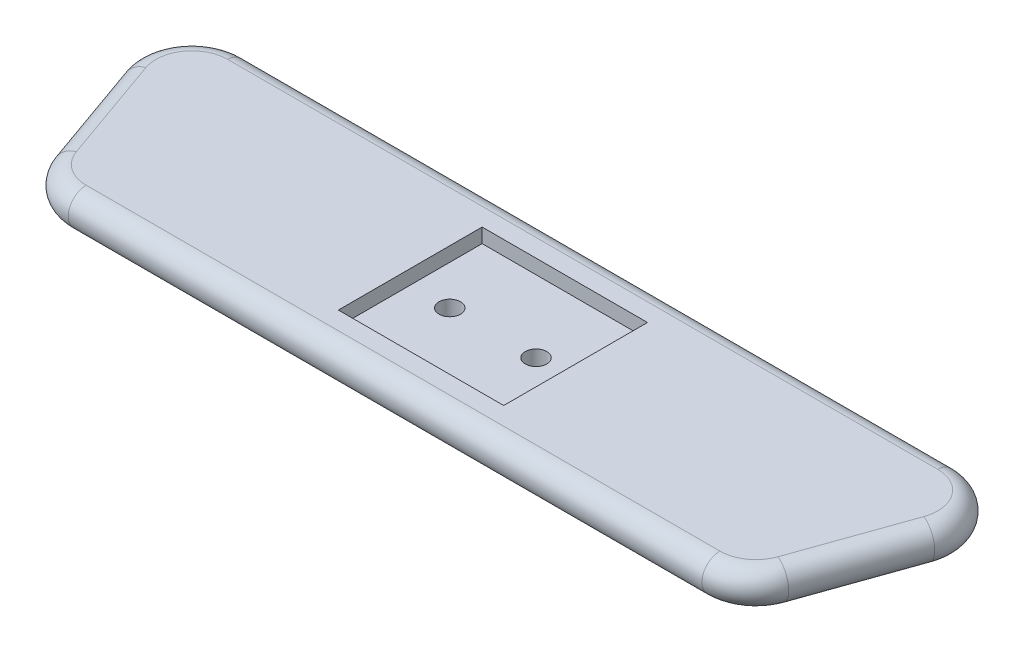
SolidWorks part; units mm, degrees
ref_plane "Front Plane" through (0, 0, 0) normal (0, 0, 1) x (1, 0, 0)
ref_plane "Top Plane" through (0, 0, 0) normal (0, 1, 0) x (1, 0, 0)
ref_plane "Right Plane" through (0, 0, 0) normal (1, 0, 0) x (0, 0, -1)
sketch "Sketch1" plane through (0, 0, 0) normal (0, 1, 0) x (1, 0, 0)
  line L0 (-112.9151, 15) -> (-102.2916, -15)
  line L1 (-98.7755, 35.0071) -> (98.7755, 35.0071)
  line L3 (-88.1519, -24.9929) -> (88.1519, -24.9929)
  line L5 (0, 35.0071) -> (0, 0) construction
  line L6 (0, 0) -> (107.6033, 0) construction
  line L7 (112.9151, 15) -> (102.2916, -15)
  arc A0 (102.2916, -15) -> (88.1519, -24.9929) centre (88.1519, -9.9929) cw
  arc A1 (98.7755, 35.0071) -> (112.9151, 15) centre (98.7755, 20.0071) cw
  arc A2 (-102.2916, -15) -> (-88.1519, -24.9929) centre (-88.1519, -9.9929) ccw
  arc A3 (-98.7755, 35.0071) -> (-112.9151, 15) centre (-98.7755, 20.0071) ccw
  point P0 (0, 0)
  point P13 (120, 35.0071)
  point P18 (-120, 35.0071)
  dimension "D2" = 15
  dimension "D1" = 240
  dimension "D3" = 70.5
  dimension "D4" = 70.5
  dimension "D5" = 60
extrude "Boss-Extrude1" add sketch "Sketch1" along normal blind 10
fillet "Fillet1" 2 edges at (0, 10, 24.9929) (0, 0, 24.9929) type full round first side face at (0, 10, -2.8572) second side face at (0, 0, -2.8572) middle face at (0, 5, 24.9929)
sketch "Sketch2" plane through (0, 10, 0) normal (0, 1, 0) x (1, 0, 0)
  line L0 (98.7755, 35.0071) -> (-98.7755, 35.0071) construction
  line L1 (-23, 25.0071) -> (23, 25.0071)
  line L2 (-23, 25.0071) -> (-23, -14.9929)
  line L3 (-23, -14.9929) -> (23, -14.9929)
  line L4 (23, 25.0071) -> (23, -14.9929)
  line L5 (-23, 25.0071) -> (23, -14.9929) construction
  line L6 (-23, -14.9929) -> (23, 25.0071) construction
  line L7 (0, 5.0071) -> (0, 35.0071) construction
  circle A0 centre (-12, 5.0071) radius 3
  circle A1 centre (12, 5.0071) radius 3
  point P0 (0, 5.0071)
  point P13 (0, 0)
  point P14 (0, 0)
  point P15 (0, 0)
  point P16 (0, 0)
  dimension "D4" = 12
  dimension "D6" = 6
  dimension "D1" = 46
  dimension "D2" = 40
  dimension "D3" = 30
  dimension "D5" = 12
extrude "Cut-Extrude5" cut sketch "Sketch2" against normal blind 4
extrude "Cut-Extrude6" cut sketch "Sketch2<6>" against normal up to next contours A0 | A1 region at (-12, 10, -5.0071) region at (12, 10, -5.0071)
sketch "Sketch2<6>" plane through (0, 10, 0) normal (0, 1, 0) x (1, 0, 0) same geometry as "Sketch2"
sketch "Sketch5" plane through (0, 0, 0) normal (0, -1, 0) x (1, 0, 0)
  line L0 (0, -5.0071) -> (-80.8226, -5.0071) construction
  line L1 (0, -5.0071) -> (0, 19.9929) construction
  line L2 (88.1519, 19.9929) -> (-88.1519, 19.9929) construction
  circle A0 centre (-70, 2.9929) radius 2
  circle A1 centre (-70, -13.0071) radius 2
  circle A2 centre (70, -13.0071) radius 2
  circle A3 centre (70, 2.9929) radius 2
  dimension "D3" = 4
  dimension "D1" = 30
  dimension "D2" = 8
  dimension "D4" = 70
extrude "Cut-Extrude7" cut sketch "Sketch5" against normal blind 8
